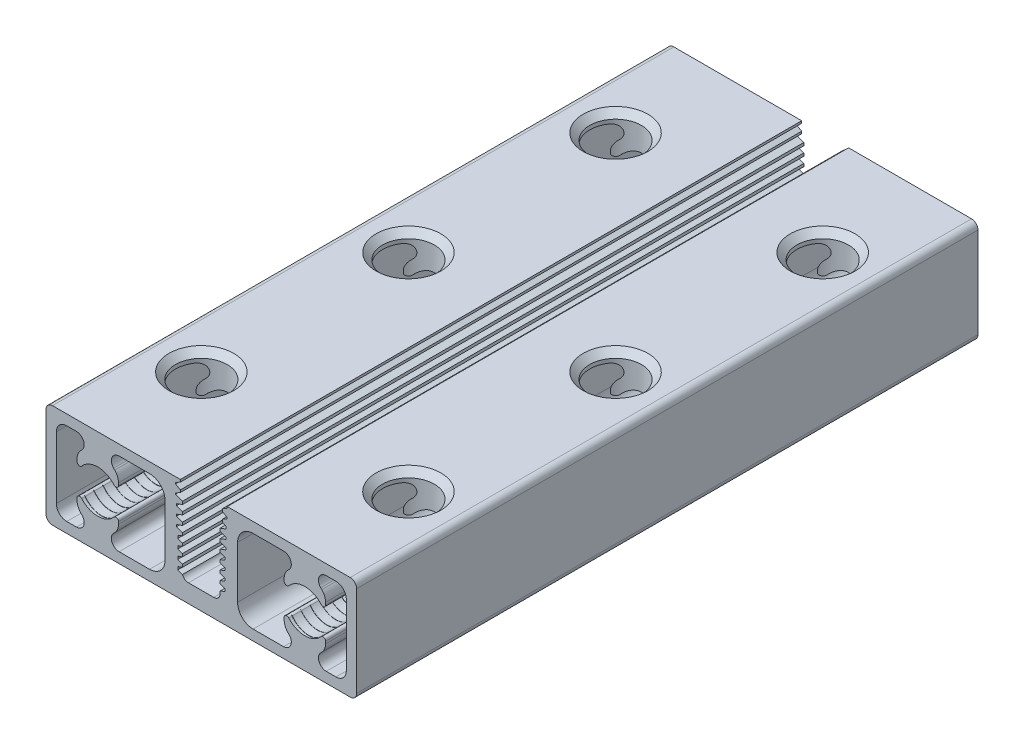
SolidWorks part; units mm, degrees
ref_plane "前视" through (0, 0, 0) normal (0, 0, 1) x (1, 0, 0)
ref_plane "上视" through (0, 0, 0) normal (0, 1, 0) x (1, 0, 0)
ref_plane "右视" through (0, 0, 0) normal (1, 0, 0) x (0, 0, -1)
sketch "草图1" plane through (0, 0, 0) normal (0, 0, 1) x (1, 0, 0)
  line L0 (-1.62, 9.9841) -> (-1.62, -0.2904) construction
  line L1 (-1.77, 9.2519) -> (-1.77, -0.5819) construction
  line L2 (-1.62, 7.825) -> (-2, 7.6056)
  line L3 (-2, -0.1994) -> (-2, 9.7651) construction
  line L4 (-2, 7.6056) -> (-2, 7.5194)
  line L5 (-2, 7.5194) -> (-1.62, 7.3)
  line L6 (-1.62, 7.3) -> (-1.62, 7.125)
  line L7 (2, 7.18) -> (1.62, 6.9606)
  line L8 (1.62, 6.9606) -> (1.62, 6.7856)
  line L9 (1.62, 6.7856) -> (1.92, 6.6124)
  line L10 (1.46, 5.5835) -> (1.46, 5.3628)
  line L11 (2, 6.48) -> (1.46, 6.1682) construction
  line L12 (-1.62, 7.825) -> (-2.4773, 7.3301) construction
  line L13 (1.46, 6.178) -> (2, 5.8662) construction
  line L14 (-1.62, 7.3) -> (-2.446, 7.7769) construction
  line L15 (2, 5.8662) -> (2, 5.78) construction
  line L16 (1.92, 5.1953) -> (1.46, 5.3628)
  line L17 (1.92, 5.1953) -> (1.92, 5.0509)
  line L18 (1.92, 5.0509) -> (1.46, 4.8835)
  line L19 (-1.62, 7.125) -> (-2, 6.9056)
  line L20 (-2, 6.9056) -> (-2, 6.8194)
  line L21 (-2, 6.8194) -> (-1.46, 6.5076) construction
  line L22 (-1.92, 6.2347) -> (-1.92, 6.0903)
  line L23 (-1.46, 6.5174) -> (-2, 6.2056) construction
  line L24 (1.92, 9.1223) -> (1.92, 0.2789) construction
  line L25 (1.46, 2.0835) -> (1.46, 1.4)
  line L26 (-12, 0) -> (12, 0)
  line L27 (-8, 4) -> (-3.9085, 4) construction
  line L28 (1.46, 9.2425) -> (1.46, 1.5701) construction
  line L29 (-9.6, 5.3858) -> (-9.6, 4.4031)
  line L30 (-1.62, 8) -> (-12, 8)
  line L31 (12, 8) -> (2, 8)
  line L32 (-8, 4) -> (-8, 7.125) construction
  line L33 (-6.1, 7.2) -> (-2.8, 7.2)
  line L34 (1.92, 6.6124) -> (1.92, 6.4509)
  line L35 (-1.62, 7.825) -> (-1.62, 8)
  line L36 (0, 0) -> (0, 10.8168) construction
  line L37 (1.62, 9.9841) -> (1.62, -0.2904) construction
  line L38 (1.77, 9.2519) -> (1.77, -0.5819) construction
  line L39 (2, -0.1994) -> (2, 9.7651) construction
  line L40 (-2.8, 7.2) -> (-2.8, 0.8)
  line L41 (-9.9, 7.2) -> (-11.2, 7.2)
  line L42 (-12, 8) -> (-12, 0)
  line L43 (-11.2, 7.2) -> (-11.2, 0.8)
  line L44 (1.46, 4.8835) -> (1.46, 4.6628)
  line L45 (-1.46, 1.4) -> (0, 1.4)
  line L46 (2, 7.88) -> (1.62, 7.6606)
  line L47 (1.62, 7.6606) -> (1.62, 7.4856)
  line L48 (1.62, 7.4856) -> (2, 7.2662)
  line L49 (2, 7.2662) -> (2, 7.18)
  line L50 (-1.46, 9.2425) -> (-1.46, 1.5701) construction
  line L51 (-1.92, 9.1223) -> (-1.92, 0.2789) construction
  line L52 (-1.46, 6.5076) -> (-1.46, 6.5174) construction
  line L53 (-6.4, 5.3858) -> (-6.4, 4.4031)
  line L54 (-6.1, 0.8) -> (-2.8, 0.8)
  line L55 (-6.4, 2.6142) -> (-6.4, 3.5969)
  line L56 (-9.6, 2.6142) -> (-9.6, 3.5969)
  line L57 (-9.9, 0.8) -> (-11.2, 0.8)
  line L58 (9.9, 0.8) -> (11.2, 0.8)
  line L59 (9.6, 2.6142) -> (9.6, 3.5969)
  line L60 (1.46, 6.1682) -> (1.46, 6.178) construction
  line L61 (6.4, 2.6142) -> (6.4, 3.5969)
  line L62 (6.1, 0.8) -> (2.8, 0.8)
  line L63 (2.8, 7.2) -> (2.8, 0.8)
  line L64 (1.92, 5.8953) -> (1.92, 5.7509)
  line L65 (6.1, 7.2) -> (2.8, 7.2)
  line L66 (6.4, 5.3858) -> (6.4, 4.4031)
  line L67 (9.6, 5.3858) -> (9.6, 4.4031)
  line L68 (1.82, 4.5317) -> (1.46, 4.6628)
  line L69 (9.9, 7.2) -> (11.2, 7.2)
  line L70 (1.92, 4.4953) -> (1.92, 4.3509) construction
  line L71 (1.82, 4.3145) -> (1.46, 4.1835)
  line L72 (1.46, 4.1835) -> (1.46, 3.9628)
  line L73 (1.82, 3.8317) -> (1.46, 3.9628)
  line L74 (1.92, 3.7953) -> (1.92, 3.6509) construction
  line L75 (11.2, 7.2) -> (11.2, 0.8)
  line L76 (-1.82, 4.5891) -> (-1.82, 1.2372) construction
  line L77 (0, 1.4) -> (1.46, 1.4)
  line L78 (1.82, 3.6145) -> (1.46, 3.4835)
  line L79 (1.46, 3.4835) -> (1.46, 3.2628)
  line L80 (1.82, 3.1317) -> (1.46, 3.2628)
  line L81 (1.92, 3.0953) -> (1.92, 2.9509) construction
  line L82 (2, 7.88) -> (2, 8)
  line L83 (1.82, 2.9145) -> (1.46, 2.7835)
  line L84 (-1.82, 4.1711) -> (-1.82, 3.9539)
  line L85 (12, 8) -> (12, 0)
  line L86 (1.46, 2.7835) -> (1.46, 2.5628)
  line L87 (1.82, 2.4317) -> (1.46, 2.5628)
  line L88 (1.92, 2.3953) -> (1.92, 2.2509) construction
  line L89 (-1.82, 3.2539) -> (-1.82, 3.4711)
  line L90 (2, 8) -> (-1.62, 8) construction
  line L91 (-1.82, 2.5539) -> (-1.82, 2.7711)
  line L92 (-1.82, 1.8539) -> (-1.82, 2.0711)
  line L93 (1.82, 4.5891) -> (1.82, 1.2372) construction
  line L94 (1.82, 2.2145) -> (1.82, 2.4317)
  line L95 (1.82, 2.2145) -> (1.46, 2.0835)
  line L96 (1.82, 2.9145) -> (1.82, 3.1317)
  line L97 (-1.46, 5.7022) -> (-1.46, 5.9228)
  line L98 (1.82, 3.6145) -> (1.82, 3.8317)
  line L99 (1.82, 4.3145) -> (1.82, 4.5317)
  line L100 (-9.3071, 6.0929) -> (-9.2243, 6.1757)
  line L101 (-9.9, 7.2) -> (-9.6485, 7.2)
  line L102 (-6.1, 7.2) -> (-6.3515, 7.2)
  line L103 (-6.6929, 6.0929) -> (-6.7757, 6.1757)
  line L104 (-6.1, 0.8) -> (-6.3515, 0.8)
  line L105 (-6.6929, 1.9071) -> (-6.7757, 1.8243)
  line L106 (-9.9, 0.8) -> (-9.6485, 0.8)
  line L107 (-9.3071, 1.9071) -> (-9.2243, 1.8243)
  line L108 (9.3071, 1.9071) -> (9.2243, 1.8243)
  line L109 (9.9, 0.8) -> (9.6485, 0.8)
  line L110 (6.6929, 1.9071) -> (6.7757, 1.8243)
  line L111 (6.1, 0.8) -> (6.3515, 0.8)
  line L112 (6.1, 7.2) -> (6.3515, 7.2)
  line L113 (6.6929, 6.0929) -> (6.7757, 6.1757)
  line L114 (-2, 6.8194) -> (-1.46, 6.6228)
  line L115 (-1.92, 6.2347) -> (-1.46, 6.4022)
  line L116 (-1.92, 6.0903) -> (-1.46, 5.9228)
  line L117 (9.9, 7.2) -> (9.6485, 7.2)
  line L118 (-1.46, 6.4022) -> (-1.46, 6.6228)
  line L119 (9.3071, 6.0929) -> (9.2243, 6.1757)
  line L124 (1.92, 6.4509) -> (1.46, 6.2835)
  line L125 (1.92, 5.8953) -> (1.46, 6.0628)
  line L126 (1.92, 5.7509) -> (1.46, 5.5835)
  line L127 (1.46, 6.2835) -> (1.46, 6.0628)
  line L128 (2, 6.5662) -> (2, 6.48) construction
  line L133 (-1.62, 6.6) -> (-1.62, 6.425) [skipped]
  line L134 (-1.62, 5.9) -> (-1.62, 5.725) [skipped]
  line L140 (-2, 6.2056) -> (-2, 6.1194) [skipped]
  line L146 (2, 6.5662) -> (2, 6.48) [skipped]
  line L147 (1.62, 6.2606) -> (1.62, 6.0856) [skipped]
  line L148 (2, 5.8662) -> (2, 5.78) [skipped]
  line L160 (-2, 6.1194) -> (-1.5, 5.8307) [skipped]
  line L172 (-1.92, 5.5347) -> (-1.46, 5.7022)
  line L181 (-1.92, 5.5347) -> (-1.92, 5.3903)
  line L182 (-1.92, 5.3903) -> (-1.46, 5.2228)
  line L183 (-1.46, 5.0022) -> (-1.46, 5.2228)
  line L184 (-1.92, 4.8347) -> (-1.46, 5.0022)
  line L185 (-1.92, 4.8347) -> (-1.92, 4.6903)
  line L186 (-1.92, 4.6903) -> (-1.46, 4.5228)
  line L187 (-1.46, 4.3022) -> (-1.46, 4.5228)
  line L188 (-1.82, 4.1711) -> (-1.46, 4.3022)
  line L189 (-1.92, 4.1347) -> (-1.92, 3.9903) construction
  line L190 (-1.82, 3.9539) -> (-1.46, 3.8228)
  line L191 (-1.46, 3.6022) -> (-1.46, 3.8228)
  line L192 (-1.82, 3.4711) -> (-1.46, 3.6022)
  line L193 (-1.92, 3.4347) -> (-1.92, 3.2903) construction
  line L194 (-1.82, 3.2539) -> (-1.46, 3.1228)
  line L195 (-1.46, 2.9022) -> (-1.46, 3.1228)
  line L196 (-1.82, 2.7711) -> (-1.46, 2.9022)
  line L197 (-1.92, 2.7347) -> (-1.92, 2.5903) construction
  line L198 (-1.82, 2.5539) -> (-1.46, 2.4228)
  line L199 (-1.46, 2.2022) -> (-1.46, 2.4228)
  line L200 (-1.82, 2.0711) -> (-1.46, 2.2022)
  line L201 (-1.92, 2.0347) -> (-1.92, 1.8903) construction
  line L202 (-1.82, 1.8539) -> (-1.46, 1.7228)
  line L203 (-1.46, 1.4) -> (-1.46, 1.7228)
  line L211 (-1.92, 1.1903) -> (-1.46, 1.0228) [skipped]
  line L212 (-1.92, 1.3347) -> (-1.92, 1.1903) [skipped]
  line L213 (-1.92, 1.3347) -> (-1.46, 1.5022) [skipped]
  arc A0 (-9.6, 3.5969) -> (-6.4, 3.5969) centre (-8, 4) ccw
  arc A1 (-6.4, 4.4031) -> (-9.6, 4.4031) centre (-8, 4) ccw
  arc A2 (9.6, 3.5969) -> (6.4, 3.5969) centre (8, 4) cw
  arc A3 (6.4, 4.4031) -> (9.6, 4.4031) centre (8, 4) cw
  circle A4 centre (-8, 4) radius 2 construction
  arc A5 (-9.2243, 6.1757) -> (-9.6485, 7.2) centre (-9.6485, 6.6) ccw
  arc A6 (-6.7757, 6.1757) -> (-6.3515, 7.2) centre (-6.3515, 6.6) cw
  arc A7 (-6.7757, 1.8243) -> (-6.3515, 0.8) centre (-6.3515, 1.4) ccw
  arc A8 (-9.2243, 1.8243) -> (-9.6485, 0.8) centre (-9.6485, 1.4) cw
  arc A9 (9.2243, 1.8243) -> (9.6485, 0.8) centre (9.6485, 1.4) ccw
  arc A10 (6.7757, 1.8243) -> (6.3515, 0.8) centre (6.3515, 1.4) cw
  arc A11 (6.7757, 6.1757) -> (6.3515, 7.2) centre (6.3515, 6.6) ccw
  arc A12 (9.2243, 6.1757) -> (9.6485, 7.2) centre (9.6485, 6.6) cw
  arc A13 (9.6, 2.6142) -> (9.3071, 1.9071) centre (8.6, 2.6142) cw
  arc A14 (6.6929, 1.9071) -> (6.4, 2.6142) centre (7.4, 2.6142) cw
  arc A15 (6.4, 5.3858) -> (6.6929, 6.0929) centre (7.4, 5.3858) cw
  arc A16 (9.3071, 6.0929) -> (9.6, 5.3858) centre (8.6, 5.3858) cw
  arc A17 (-6.4, 2.6142) -> (-6.6929, 1.9071) centre (-7.4, 2.6142) cw
  arc A18 (-9.6, 2.6142) -> (-9.3071, 1.9071) centre (-8.6, 2.6142) ccw
  arc A19 (-6.4, 5.3858) -> (-6.6929, 6.0929) centre (-7.4, 5.3858) ccw
  arc A20 (-9.6, 5.3858) -> (-9.3071, 6.0929) centre (-8.6, 5.3858) cw
  point P47 (0, -6)
  point P62 (0, -6)
  point P72 (-2.8, 4)
  point P81 (-11.2, 4)
  point P204 (9.6, 2.2)
  point P209 (6.4, 2.2)
  point P212 (6.4, 5.8)
  point P215 (9.6, 5.8)
  point P218 (-6.4, 2.2)
  point P227 (-9.6, 2.2)
  point P230 (-6.4, 5.8)
  point P233 (-9.6, 5.8)
  dimension "D16" = 60
  dimension "D20" = 60
  dimension "D27" = 8
  dimension "D28" = 60
  dimension "D40" = 1.6
  dimension "D47" = 70
  dimension "D12" = 3.3
  dimension "D48" = 4
  dimension "D49" = 0.6
  dimension "D53" = 1
  dimension "D1" = 1.62
  dimension "D2" = 1.77
  dimension "D3" = 2
  dimension "D4" = 60
  dimension "D5" = 60
  dimension "D6" = 0.175
  dimension "D7" = 0.0862
  dimension "D8" = 0.7
  dimension "D11" = 60
  dimension "D13" = 0.175
  dimension "D14" = 120
  dimension "D15" = 12
  dimension "D17" = 0.7
  dimension "D18" = 3
  dimension "D19" = 1.4
  dimension "D10" = 0.175
  dimension "D21" = 0.3394
  dimension "D22" = 0.12
  dimension "D23" = 4
  dimension "D24" = 8
  dimension "D25" = 1.46
  dimension "D26" = 1.92
  dimension "D29" = 60
  dimension "D30" = 6
  dimension "D31" = 0.2207
  dimension "D32" = 0.8
  dimension "D33" = 0.8
  dimension "D34" = 0.7
  dimension "D35" = 0.0098
  dimension "D36" = 0.0862
  dimension "D37" = 70
  dimension "D38" = 70
  dimension "D39" = 2.8
  dimension "D41" = 1.3
  dimension "D42" = 3.3
  dimension "D43" = 1.82
  dimension "D44" = 1.82
  dimension "D45" = 45
  dimension "D46" = 1.4
  dimension "D50" = 8
  dimension "D51" = 70
  dimension "D52" = 0.7
  dimension "D59" = 70
  dimension "D60" = 70
  dimension "D61" = 0.7
  dimension "D63" = 0.7
  dimension "D9" = 3
extrude "凸台-拉伸1" add sketch "草图1" along normal blind 48
fillet "Fillet1" radius 0.2 8 edges at (-9.6, 3.5969, 24) (-6.4, 3.5969, 24) (6.4, 3.5969, 24) (9.6, 3.5969, 24) (9.6, 4.4031, 24) (6.4, 4.4031, 24) (-6.4, 4.4031, 24) (-9.6, 4.4031, 24)
sketch "Sketch1" plane through (0, 8, 0) normal (0, 1, 0) x (1, 0, 0)
  line L0 (12, -48) -> (12, 0) construction
  line L1 (12, -48) -> (2, -48) construction
  line L2 (-12, -48) -> (-12, 0) construction
  line L3 (-1.62, -48) -> (-12, -48) construction
  circle A0 centre (8, -40) radius 2
  circle A1 centre (-8, -40) radius 2
  dimension "D1" = 4
  dimension "D4" = 4
  dimension "D2" = 4
  dimension "D3" = 8
  dimension "D5" = 4
  dimension "D6" = 8
extrude "Cut-Extrude1" cut sketch "Sketch1" against normal through all
chamfer "Chamfer1" distance 0.5 angle 45 4 edges at (6, 0, 40) (6, 8, 40) (-10, 0, 40) (-10, 8, 40)
fillet "圆角1" radius 0.5 4 edges at (12, 0, 24) (12, 8, 24) (-12, 0, 24) (-12, 8, 24)
fillet "圆角2" radius 1.2 4 edges at (2.8, 7.2, 24) (2.8, 0.8, 24) (-2.8, 0.8, 24) (-2.8, 7.2, 24)
fillet "圆角3" radius 0.8 4 edges at (11.2, 0.8, 24) (11.2, 7.2, 24) (-11.2, 0.8, 24) (-11.2, 7.2, 24)
fillet "圆角4" radius 0.5 2 edges at (-1.46, 1.4, 24) (1.46, 1.4, 24)
pattern_linear "阵列(线性)1" count 3 spacing 16 along (0, 0, -1) of "Cut-Extrude1", "Chamfer1"
sketch "草图2" plane through (0, 0, 48) normal (0, 0, 1) x (1, 0, 0)
  circle A0 centre (-8, 4) radius 1.65
  arc A1 (-6.7514, 5.0786) -> (-9.2486, 5.0786) centre (-8, 4) ccw construction
curve "螺旋线/涡状线1" pitch 0.7 height 6 turns 8.5714
sketch "草图3" plane through (0, 0, 48) normal (0, 0, 1) x (1, 0, 0)
  circle A0 centre (8, 4) radius 1.65
  arc A1 (9.2486, 5.0786) -> (6.7514, 5.0786) centre (8, 4) ccw construction
curve "螺旋线/涡状线2" pitch 0.7 height 6 turns 8.5714
ref_plane "基准面1" through (0, 4, 0) normal (0, -1, 0) x (-1, 0, 0)
sketch "草图4" plane through (0, 4, 0) normal (0, -1, 0) x (-1, 0, 0)
  circle A0 centre (6.35, -48) radius 0.01
  dimension "D1" = 0.02
sweep "切除-扫描1" cut profiles "草图4" path "螺旋线/涡状线1"
sketch "草图5" plane through (0, 4, 0) normal (0, -1, 0) x (-1, 0, 0)
  circle A0 centre (-9.65, -48) radius 0.01
  dimension "D1" = 0.02
sweep "切除-扫描2" cut profiles "草图5" path "螺旋线/涡状线2"
ref_plane "基准面2" through (0, 0, 24) normal (0, 0, 1) x (1, 0, 0)
mirror "镜向1" about plane through (0, 0, 24) normal (0, 0, 1) of "切除-扫描2", "切除-扫描1"
equation "\"length\"= \"D1@凸台-拉伸1\""
